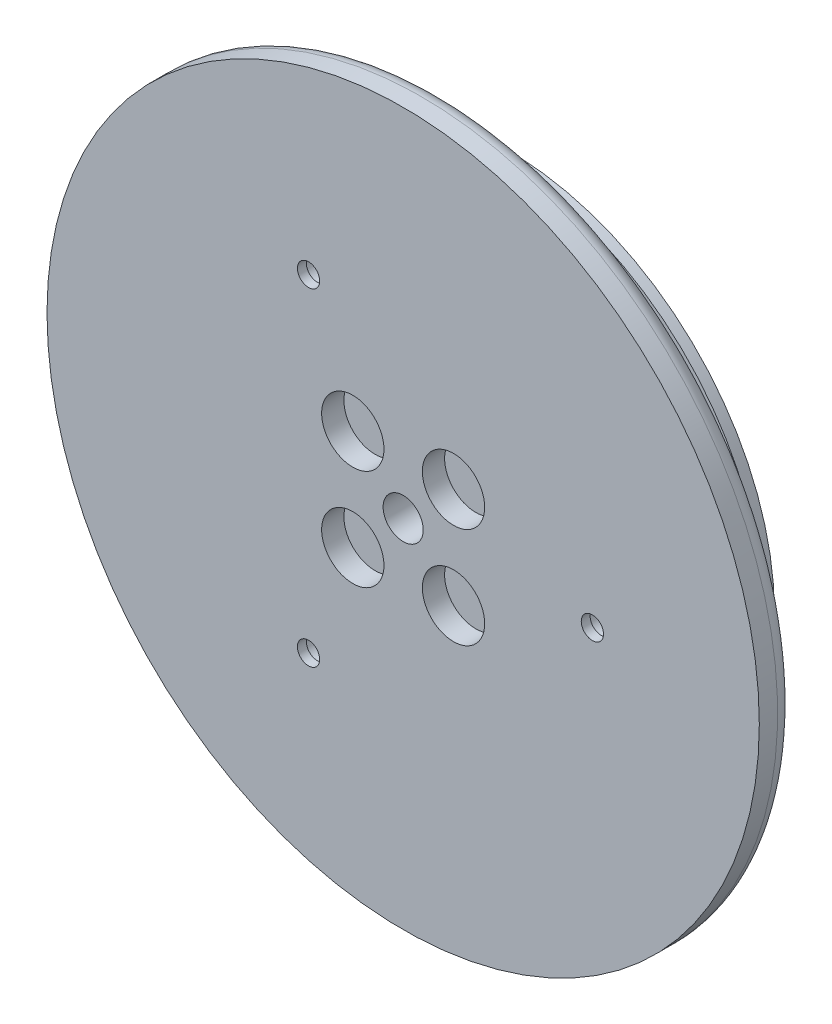
SolidWorks part; units mm, degrees
other "Main Coupler Piece"
other "back piece"
other "insert1"
other "insert2"
other "insert3"
ref_plane "Front Plane" through (0, 0, 0) normal (0, 0, 1) x (1, 0, 0)
ref_plane "Top Plane" through (0, 0, 0) normal (0, 1, 0) x (1, 0, 0)
ref_plane "Right Plane" through (0, 0, 0) normal (1, 0, 0) x (0, 0, -1)
sketch "Sketch1" plane through (0, 0, 0) normal (0, 0, 1) x (1, 0, 0)
  circle A0 centre (0, 0) radius 12.5
  circle A1 centre (0, 0) radius 30
  dimension "D1" = 25
  dimension "D2" = 60
extrude "Boss-Extrude1" add sketch "Sketch1" along normal blind 6
sketch "Sketch2" plane through (0, 0, 6) normal (0, 0, 1) x (1, 0, 0)
  line L1 (-5.656, 5.6577) -> (5.656, 5.6577) construction
  line L2 (-5.656, 5.6577) -> (-5.656, -5.6577) construction
  line L3 (-5.656, -5.6577) -> (5.656, -5.6577) construction
  line L4 (5.656, 5.6577) -> (5.656, -5.6577) construction
  circle A0 centre (0, 0) radius 2.25
  circle A1 centre (-5.656, 5.6577) radius 1.5
  circle A2 centre (-5.656, -5.6577) radius 1.5
  circle A3 centre (5.656, -5.6577) radius 1.5
  circle A4 centre (5.656, 5.6577) radius 1.5
  circle A5 centre (0, 0) radius 40
  point P15 (0, -5.6577)
  point P16 (-5.656, 0)
  dimension "D1" = 4.5
  dimension "D4" = 3
  dimension "D5" = 80
  dimension "D2" = 16
  dimension "D3" = 11.3154
extrude "Boss-Extrude2" add sketch "Sketch2" along normal blind 4
sketch "Sketch3" plane through (0, 0, 10) normal (0, 0, 1) x (1, 0, 0)
  circle A0 centre (-5.656, 5.6577) radius 3.5
  circle A1 centre (5.656, 5.6577) radius 3.5
  circle A2 centre (5.656, -5.6577) radius 3.5
  circle A3 centre (-5.656, -5.6577) radius 3.5
  dimension "D1" = 7
extrude "Cut-Extrude1" cut sketch "Sketch3" against normal blind 2.5
sketch "Sketch4" plane through (0, 0, 0) normal (0, 0, -1) x (-1, 0, 0)
  circle A0 centre (-20, 0) radius 5.15
  circle A1 centre (0, -20) radius 5.15
  circle A2 centre (0, 0) radius 20 construction
  circle A3 centre (0, 0) radius 20 construction
  circle A4 centre (20, 0) radius 5.15
  circle A5 centre (0, 0) radius 20 construction
  circle A6 centre (0, 20) radius 5.15
  circle A7 centre (0, 0) radius 20 construction
  circle A8 centre (0, 20) radius 2.65 construction
  circle A9 centre (14.1421, 14.1421) radius 2.65
  circle A10 centre (0, 0) radius 20 construction
  circle A11 centre (20, 0) radius 2.65 construction
  circle A12 centre (0, 0) radius 20 construction
  circle A13 centre (14.1421, -14.1421) radius 2.65
  circle A14 centre (0, 0) radius 20 construction
  circle A15 centre (0, -20) radius 2.65 construction
  circle A16 centre (0, 0) radius 20 construction
  circle A17 centre (-14.1421, -14.1421) radius 2.65
  circle A18 centre (0, 0) radius 20 construction
  circle A19 centre (-20, 0) radius 2.65 construction
  circle A20 centre (0, 0) radius 20 construction
  circle A21 centre (-14.1421, 14.1421) radius 2.65
  circle A22 centre (0, 0) radius 20 construction
  point P17 (0, 0)
  point P39 (0, 0)
  dimension "D1" = 10.3
  dimension "D2" = 40
  dimension "D4" = 5.3
  dimension "D3" = 4
  dimension "D5" = 8
extrude "Cut-Extrude2" cut sketch "Sketch4" against normal blind 3 contours A4
sketch "Sketch5" plane through (0, 0, 7.5) normal (0, 0, 1) x (1, 0, 0)
  circle A0 centre (-5.656, 5.6577) radius 3.5
  circle A1 centre (5.656, 5.6577) radius 3.5
  circle A2 centre (-5.656, -5.6577) radius 3.5
  circle A3 centre (5.656, -5.6577) radius 3.5
extrude "Boss-Extrude3" add sketch "Sketch5" against normal blind 0.2
sketch "Sketch6" plane through (0, 0, 0) normal (0, 0, -1) x (-1, 0, 0)
  circle A0 centre (-21.25, 0) radius 1.25
  circle A1 centre (0, 0) radius 12.5 construction
  circle A2 centre (10.625, 18.403) radius 1.25
  circle A3 centre (10.625, -18.403) radius 1.25
  circle A4 centre (0, 0) radius 30 construction
  point P12 (0, 0)
  dimension "D1" = 21.25
  dimension "D2" = 2.5
  dimension "D3" = 3
extrude "Cut-Extrude3" cut sketch "Sketch6" against normal blind 10
sketch "Sketch7" plane through (0, 0, 0) normal (0, 0, -1) x (-1, 0, 0)
  circle A0 centre (-21.25, 0) radius 3.125
  circle A1 centre (10.625, 18.403) radius 3.125
  circle A2 centre (10.625, -18.403) radius 3.125
  dimension "D1" = 6.25
extrude "Cut-Extrude4" cut sketch "Sketch7" against normal offset from surface (9 mm away) 1 up to face at (20, 0, 10)
sketch "Sketch8" plane through (0, 0, 0) normal (0, 0, -1) x (-1, 0, 0)
  circle A0 centre (20, 0) radius 2
  circle A1 centre (20, 0) radius 5.15 construction
  circle A2 centre (-10, -17.3205) radius 2
  circle A3 centre (-10, 17.3205) radius 2
  circle A4 centre (0, 0) radius 30 construction
  circle A5 centre (17.3205, -10) radius 2
  circle A6 centre (10, -17.3205) radius 2
  circle A7 centre (0, -20) radius 2
  circle A8 centre (-10, -17.3205) radius 2
  circle A9 centre (-17.3205, -10) radius 2
  circle A10 centre (-20, 0) radius 2
  circle A11 centre (-17.3205, 10) radius 2
  circle A12 centre (-10, 17.3205) radius 2
  circle A13 centre (0, 20) radius 2
  circle A14 centre (10, 17.3205) radius 2
  circle A15 centre (17.3205, 10) radius 2
  circle A16 centre (0, 0) radius 30 construction
  point P11 (0, 0)
  point P36 (0, 0)
  dimension "D1" = 4
  dimension "D2" = 3
  dimension "D3" = 12
extrude "Cut-Extrude5" cut sketch "Sketch8" against normal offset from surface (8 mm away) 2 contours A11 | A9 | A15 | A5 | A13 | A7 up to face at (20, 0, 10)
sketch "Sketch9" plane through (0, 0, 0) normal (0, 0, -1) x (-1, 0, 0)
  circle A0 centre (-21.25, 0) radius 3
  circle A1 centre (10.625, 18.403) radius 3
  circle A2 centre (10.625, -18.403) radius 3
  dimension "D1" = 6
extrude "Boss-Extrude4" add sketch "Sketch9" along normal blind 0.5 separate body
sketch "Sketch10" plane through (0, 0, -0.5) normal (0, 0, -1) x (-1, 0, 0)
  circle A0 centre (20, 0) radius 5.15
  circle A7 centre (20, 0) radius 5.15 construction
  circle A8 centre (-17.3205, 10) radius 2
  circle A9 centre (0, 20) radius 2
  circle A10 centre (17.3205, 10) radius 2
  circle A11 centre (17.3205, -10) radius 2
  circle A12 centre (0, -20) radius 2
  circle A13 centre (-17.3205, -10) radius 2
  circle A16 centre (20, 0) radius 5.15
  circle A17 centre (0, 0) radius 30
  circle A18 centre (0, 0) radius 12.5
  circle A19 centre (20, 0) radius 5.15
  circle M3 centre (10.625, 18.403) radius 3
sketch "Sketch11" plane through (0, 0, 9) normal (0, 0, -1) x (-1, 0, 0)
  circle A0 centre (-21.25, 0) radius 3
  circle A1 centre (10.625, 18.403) radius 3
  circle A2 centre (10.625, -18.403) radius 3
  circle A4 centre (-21.25, 0) radius 1.5
  circle A5 centre (10.625, 18.403) radius 1.5
  circle A6 centre (10.625, -18.403) radius 1.5
  dimension "D1" = 6
  dimension "D2" = 3
extrude "Boss-Extrude6" add sketch "Sketch11" along normal blind 3 separate body
extrude "Boss-Extrude7" add sketch "Sketch10" along normal blind 1.2 separate body contours A17 A18 A0 A8 A9 A10 A11 A12 A13 M3 | M3 region at (29.1515, 0, -0.5) region at (-10.625, 18.403, -0.5)
delete or keep bodies "Body-Delete/Keep 1" type delete bodies bodies 111
delete or keep bodies "Body-Delete/Keep 2" type delete bodies bodies 110
delete or keep bodies "Body-Delete/Keep 3" type delete bodies bodies 109
fillet "Fillet1" radius 10 1 edges at (30, 0, 6)
fillet "Fillet2" radius 2 1 edges at (40, 0, 6)
sketch "Sketch12" plane through (0, 0, 6) normal (0, 0, -1) x (-1, 0, 0)
  circle A0 centre (0, 0) radius 12.5
  circle A1 centre (0, 0) radius 2.25
  circle A2 centre (-5.656, 5.6577) radius 1.5
  circle A3 centre (5.656, 5.6577) radius 1.5
  circle A4 centre (5.656, -5.6577) radius 1.5
  circle A5 centre (-5.656, -5.6577) radius 1.5
extrude "Boss-Extrude8" add sketch "Sketch12" along normal blind 2
sketch "Sketch13" plane through (0, 0, -0.5) normal (0, 0, 1) x (1, 0, 0)
  circle A0 centre (21.25, 0) radius 3.125
  circle A1 centre (-10.625, 18.403) radius 3.125
  circle A2 centre (-10.625, -18.403) radius 3.125
extrude "Boss-Extrude9" add sketch "Sketch13" along normal blind 1
fillet "Fillet3" radius 1.5 3 edges at (-7.5, -18.403, 0.5) (24.375, 0, 0.5) (-7.5, 18.403, 0.5)
